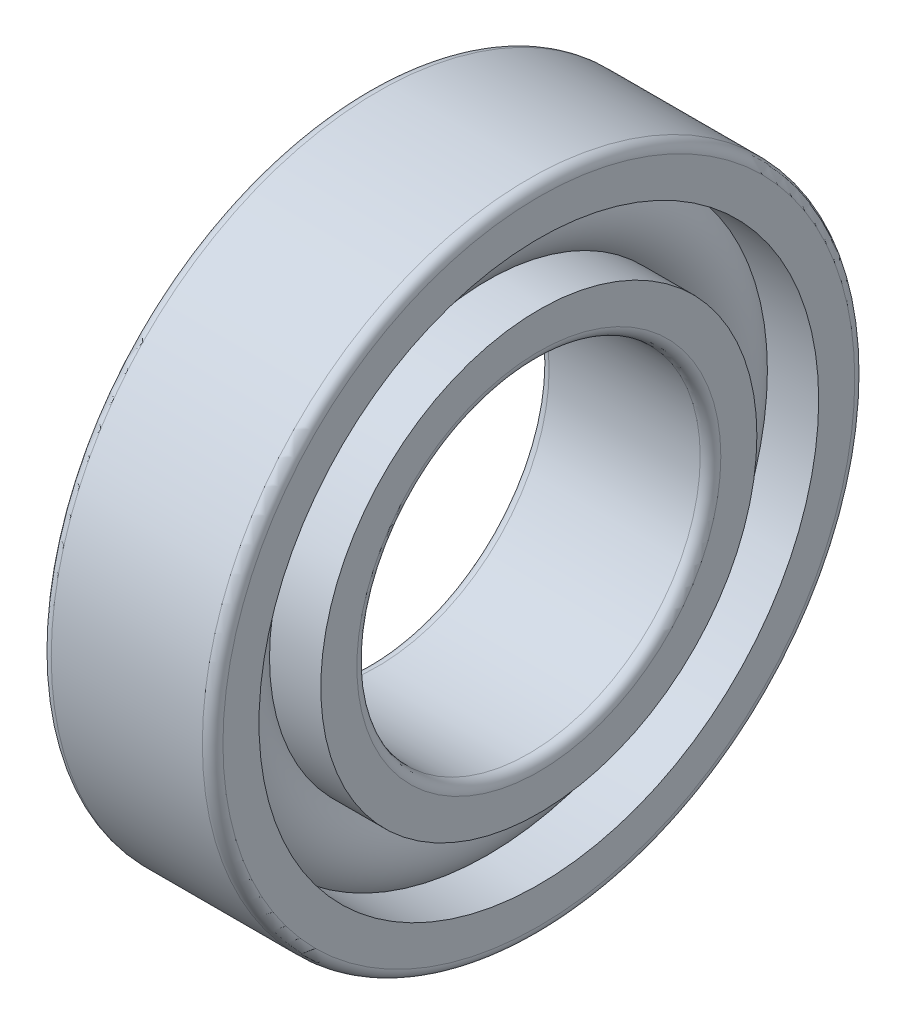
SolidWorks part; units mm, degrees
ref_plane "Plane1" through (0, 0, 0) normal (0, 0, 1) x (1, 0, 0)
ref_plane "Plane2" through (0, 0, 0) normal (0, 1, 0) x (1, 0, 0)
ref_plane "Plane3" through (0, 0, 0) normal (1, 0, 0) x (0, 0, -1)
sketch "Clipboard" plane through (0, 0, 0) normal (0, 0, 1) x (1, 0, 0)
  line L0 (-10, 0) -> (10, 0) construction
  line L1 (0, 0) -> (22.3471, -0.7804)
  line L2 (0, 0) -> (7.2456, 0.253)
  line L3 (0, 0) -> (22.3471, -0.7804)
  line L4 (0, 0) -> (-22.3573, -0.3902)
  dimension "BallCLRad" = 7.25
  dimension "Count" = 2
  dimension "Show_count" = 2
  dimension "Max_count" = 2
  dimension "Min_count" = 1
sketch "CagSpiSke" plane through (0, 0, 0) normal (0, 0, 1) x (1, 0, 0)
  line L0 (0.135, 7.025) -> (0.135, 7.475)
  line L1 (0.135, 7.475) -> (-0.135, 7.475)
  line L2 (-0.135, 7.475) -> (-0.135, 7.025)
  line L3 (-0.135, 7.025) -> (0.135, 7.025)
  line L4 (-20.6375, 0) -> (20.6375, 0) construction
  line L5 (0, 0) -> (0, 23.7692) construction
  dimension "Thickness" = 0.27
  dimension "OD" = 14.95
  dimension "ID" = 14.05
revolve "CageSpine" add sketch "CagSpiSke" angle 0.001 about L4 reverse direction yes
ref_axis "Axis1" through (-50, 0, 0) along (1, 0, 0)
sketch "CagBalSke" plane through (0, 0, 0) normal (0, 0, 1) x (1, 0, 0)
  line L0 (-1.485, 7.25) -> (1.485, 7.25)
  line L1 (-1.905, 7.25) -> (1.905, 7.25) construction
  line L2 (-10, 0) -> (10, 0) construction
  line L3 (0, 0) -> (0, 24) construction
  arc A0 (1.485, 7.25) -> (-1.485, 7.25) centre (0, 7.25) cw
  dimension "CageWallOD" = 2.97
  dimension "BallCLRad" = 7.25
revolve "CageBall" [suppressed] add sketch "CagBalSke" angle 360 about L1 reverse direction yes
pattern_circular "CageBalls" [suppressed] count 2 every 180 about axis through (-50, 0, 0) along (1, 0, 0)
sketch "CagTrmODSke" plane through (0, 0, 0) normal (0, 0, 1) x (1, 0, 0)
  line L0 (1.486, 7.475) -> (1.486, 8.736)
  line L1 (1.486, 8.736) -> (-1.486, 8.736)
  line L2 (-1.486, 8.736) -> (-1.486, 7.475)
  line L3 (-1.486, 7.475) -> (1.486, 7.475)
  line L4 (-20.6375, 0) -> (20.6375, 0) construction
  line L5 (0, 0) -> (0, 25) construction
  dimension "Width" = 2.972
  dimension "ID" = 14.95
  dimension "OD" = 17.472
revolve "CageTrimOD" [suppressed] cut sketch "CagTrmODSke" angle 360 about L4 reverse direction yes
sketch "CagTrmIDSke" plane through (0, 0, 0) normal (0, 0, 1) x (1, 0, 0)
  line L0 (1.486, 5.766) -> (1.486, 7.025)
  line L1 (1.486, 7.025) -> (-1.486, 7.025)
  line L2 (-1.486, 7.025) -> (-1.486, 5.766)
  line L3 (-1.486, 5.766) -> (1.486, 5.766)
  line L4 (-20.6375, 0) -> (20.6375, 0) construction
  line L5 (0, 0) -> (0, 25) construction
  dimension "ID" = 11.532
  dimension "OD" = 14.05
  dimension "Width" = 2.972
revolve "CageTrimID" [suppressed] cut sketch "CagTrmIDSke" angle 360 about L4 reverse direction yes
sketch "BalSimSke" plane through (0, 0, 0) normal (0, 0, 1) x (1, 0, 0)
  line L0 (-10, 0) -> (10, 0) construction
  line L1 (-10, 7.25) -> (10, 7.25) construction
  line L2 (0, 0) -> (0, 23) construction
  circle A0 centre (0, 7.25) radius 1.35
  dimension "Ball_diameter" = 2.7
  dimension "BallCLRad" = 7.25
revolve "BallsSimplified" add sketch "BalSimSke" angle 360 about L0
sketch "BalDetSke" plane through (0, 0, 0) normal (0, 0, 1) x (1, 0, 0)
  line L0 (-1.35, 7.25) -> (1.35, 7.25)
  line L1 (-1.905, 7.25) -> (1.905, 7.25) construction
  line L2 (0, 0) -> (0, 25) construction
  arc A0 (1.35, 7.25) -> (-1.35, 7.25) centre (0, 7.25) cw
  dimension "Ball_diameter" = 2.7
  dimension "BallCLRad" = 7.25
revolve "BallDetailed" [suppressed] add sketch "BalDetSke" angle 360 about L1 reverse direction yes
sketch "InnRacSke" plane through (0, 0, 0) normal (0, 0, 1) x (1, 0, 0)
  line L0 (-0.9724, 6.35) -> (-2.5, 6.35)
  line L1 (-2.5, 6.35) -> (-2.5, 5.3)
  line L2 (-2.2, 5) -> (2.2, 5)
  line L3 (2.5, 5.3) -> (2.5, 6.35)
  line L4 (2.5, 6.35) -> (0.9724, 6.35)
  line L5 (-20.6375, 0) -> (20.6375, 0) construction
  line L6 (0, 0) -> (0, 30) construction
  arc A0 (-2.5, 5.3) -> (-2.2, 5) centre (-2.2, 5.3) ccw
  arc A1 (2.2, 5) -> (2.5, 5.3) centre (2.2, 5.3) ccw
  arc A2 (0.9724, 6.35) -> (-0.9724, 6.35) centre (0, 7.25) cw
  dimension "Fillet_radius" = 0.3
  dimension "Ball_diameter" = 2.65
  dimension "ID" = 10
  dimension "OD" = 12.7
  dimension "Width" = 5
  dimension "BallCLRad" = 7.25
revolve "InnerRace" add sketch "InnRacSke" angle 360 about L5 reverse direction yes
sketch "OutRacSke" plane through (0, 0, 0) normal (0, 0, 1) x (1, 0, 0)
  line L0 (-0.9724, 8.15) -> (-2.5, 8.15)
  line L1 (-2.5, 8.15) -> (-2.5, 9.2)
  line L2 (-2.2, 9.5) -> (2.2, 9.5)
  line L3 (2.5, 9.2) -> (2.5, 8.15)
  line L4 (2.5, 8.15) -> (0.9724, 8.15)
  line L5 (-20.6375, 0) -> (20.6375, 0) construction
  line L6 (0, 0) -> (0, 30) construction
  arc A0 (-2.5, 9.2) -> (-2.2, 9.5) centre (-2.2, 9.2) cw
  arc A1 (2.2, 9.5) -> (2.5, 9.2) centre (2.2, 9.2) cw
  arc A2 (0.9724, 8.15) -> (-0.9724, 8.15) centre (0, 7.25) ccw
  dimension "Fillet_radius" = 0.3
  dimension "Ball_diameter" = 2.65
  dimension "OD" = 19
  dimension "ID" = 16.3
  dimension "Width" = 5
  dimension "BallCLRad" = 7.25
revolve "OuterRace" add sketch "OutRacSke" angle 360 about L5 reverse direction yes
pattern_circular "BallsDetailed" [suppressed] count 2 every 180 about axis through (-50, 0, 0) along (1, 0, 0)
equation "\"BallCLRad@Clipboard\" = ( \"OD@OutRacSke\" + \"ID@InnRacSke\" ) / 4"
equation "\"BallCLRad@BalSimSke\" = \"BallCLRad@Clipboard\""
equation "\"BallCLRad@BalDetSke\" = \"BallCLRad@Clipboard\""
equation "\"BallCLRad@InnRacSke\" = \"BallCLRad@Clipboard\""
equation "\"BallCLRad@OutRacSke\" = \"BallCLRad@Clipboard\""
equation "\"Ball_diameter@InnRacSke\" = \"Ball_diameter@BalDetSke\" - 0.05"
equation "\"Ball_diameter@OutRacSke\" = \"Ball_diameter@BalDetSke\" - 0.05"
equation "\"Ball_diameter@BalSimSke\" = \"Ball_diameter@BalDetSke\""
equation "\"Width@OutRacSke\" = \"Width@InnRacSke\""
equation "\"Fillet_radius@OutRacSke\" = \"Fillet_radius@InnRacSke\""
equation "\"Max_count@Clipboard\" = int( 3.14159265 / atn(( \"Ball_diameter@BalDetSke\" / 2) / sqr( \"BallCLRad@Clipboard\"  *  \"BallCLRad@Clipboard\" - ( \"Ball_diameter@BalDetSke\" / 2) *  ( \"Ball_diameter@BalDetSke\" / 2))))"
equation "\"Max_count@Clipboard\" = ((sgn( \"Max_count@Clipboard\" - \"Count@Clipboard\" )-1)*( \"Max_count@Clipboard\" - \"Count@Clipboard\" ))/-2+ \"Count@Clipboard\""
equation "\"Count@BallsDetailed\" = int( \"Show_count@Clipboard\" ) "
equation "\"Count@BallsDetailed\" = ((sgn( \"Count@BallsDetailed\" - \"Max_count@Clipboard\" )-1)*( \"Count@BallsDetailed\" - \"Max_count@Clipboard\" ))/-2+ \"Max_count@Clipboard\""
equation "\"Count@BallsDetailed\" = ((sgn( \"Count@BallsDetailed\" - \"Min_count@Clipboard\" )+1)*( \"Count@BallsDetailed\" - \"Min_count@Clipboard\"))/2 +\"Min_count@Clipboard\""
equation "\"Angle@BallsDetailed\" = 360.0 / \"Max_count@Clipboard\""
equation "\"BallCLRad@CagBalSke\" = \"BallCLRad@Clipboard\""
equation "\"Count@CageBalls\" = \"Count@BallsDetailed\""
equation "\"Angle@CageBalls\" = \"Angle@BallsDetailed\""
equation "\"Angle@CageSpine\" =  \"Angle@CageBalls\" * ( \"Count@CageBalls\" -1 + int( \"Count@CageBalls\" / \"Max_count@Clipboard\" ) )  + 0.001 -  int( \"Count@CageBalls\" / \"Max_count@Clipboard\" ) * 0.001"
equation "\"Angle@CageSpine\" =  \"Angle@CageSpine\" * int( \"Min_count@Clipboard\" / 2) + int(1 / \"Min_count@Clipboard\")  * 0.001"
equation "\"CageWallOD@CagBalSke\" =  \"Ball_diameter@BalDetSke\" * 1.1"
equation "\"Thickness@CagSpiSke\" =  \"Ball_diameter@BalDetSke\" * 0.1"
equation "\"OD@CagTrmODSke\" = \"BallCLRad@Clipboard\" * 2 + \"CageWallOD@CagBalSke\" + 0.002"
equation "\"ID@CagTrmODSke\" = \"BallCLRad@Clipboard\" * 2 + \"Ball_diameter@BalDetSke\" / 6"
equation "\"OD@CagTrmIDSke\" = \"BallCLRad@Clipboard\" * 2 - \"Ball_diameter@BalDetSke\" / 6"
equation "\"ID@CagTrmIDSke\" = \"BallCLRad@Clipboard\" * 2 - \"CageWallOD@CagBalSke\" + 0.002"
equation "\"OD@CagSpiSke\" = \"ID@CagTrmODSke\""
equation "\"ID@CagSpiSke\" = \"OD@CagTrmIDSke\""
equation "\"Width@CagTrmODSke\" = \"CageWallOD@CagBalSke\" + 0.002"
equation "\"Width@CagTrmIDSke\" = \"CageWallOD@CagBalSke\" + 0.002"
